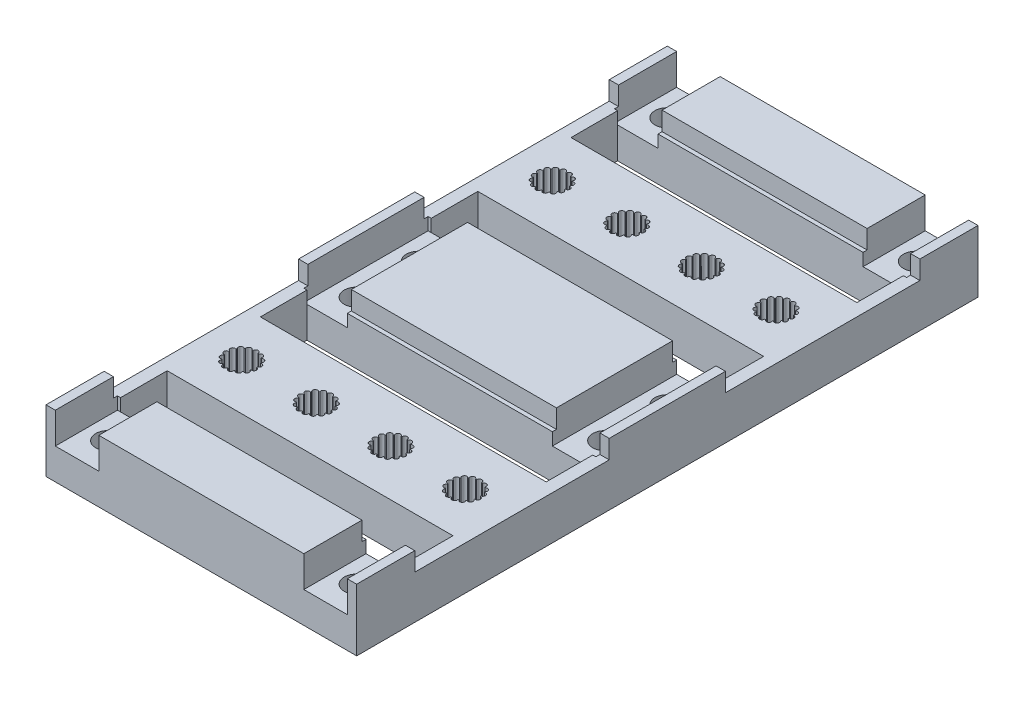
SolidWorks part; units mm, degrees
ref_plane "Front Plane" through (0, 0, 0) normal (0, 0, 1) x (1, 0, 0)
ref_plane "Top Plane" through (0, 0, 0) normal (0, 1, 0) x (1, 0, 0)
ref_plane "Right Plane" through (0, 0, 0) normal (1, 0, 0) x (0, 0, -1)
sketch "Sketch1" plane through (0, 0, 0) normal (0, 1, 0) x (1, 0, 0)
  line L0 (25, 25) -> (25, -25)
  line L1 (-20, 20) -> (20, 20)
  line L2 (-20, 20) -> (-20, -20)
  line L3 (-20, -20) -> (20, -20)
  line L4 (20, 20) -> (20, -20)
  line L5 (-20, 20) -> (20, -20) construction
  line L6 (-20, -20) -> (20, 20) construction
  line L7 (30, -16) -> (-30, -16)
  line L8 (30, -16) -> (30, 16)
  line L9 (30, 16) -> (-30, 16)
  line L10 (-30, -16) -> (-30, 16)
  line L11 (30, -16) -> (-30, 16) construction
  line L12 (30, 16) -> (-30, -16) construction
  line L13 (-25, -25) -> (25, -25)
  line L14 (-25, 25) -> (-25, -25)
  line L15 (-25, 25) -> (25, 25)
  point P0 (0, 0)
  point P6 (0, 0)
  dimension "D1" = 40
  dimension "D2" = 40
  dimension "D3" = 32
  dimension "D4" = 60
  dimension "D5" = 5
extrude "Boss-Extrude2" add sketch "Sketch1" along normal blind 10 contours L15 L0 L13 L14
sketch "Sketch2" plane through (0, 10, 0) normal (0, 1, 0) x (1, 0, 0)
  line L0 (30, -16) -> (-30, -16) construction
  line L1 (30, -16) -> (30, 16) construction
  line L2 (30, 16) -> (-30, 16) construction
  line L3 (-30, -16) -> (-30, 16) construction
  line L4 (30, -16) -> (-30, -16)
  line L5 (30, -16) -> (30, 16)
  line L6 (30, 16) -> (-30, 16)
  line L7 (-30, -16) -> (-30, 16)
  line L8 (29.65, 15.65) -> (-29.65, 15.65)
  line L9 (-29.65, -15.65) -> (-29.65, 15.65)
  line L10 (29.65, -15.65) -> (-29.65, -15.65)
  line L11 (29.65, -15.65) -> (29.65, 15.65)
  line M5 (-25, 25) -> (-25, -25)
  line M7 (25, -25) -> (25, 25)
  dimension "D1" = 0.35
extrude "Cut-Extrude1" cut sketch "Sketch2" against normal blind 3 contours L10 L8 M7 M5 | L10 L8 L9 M5 | L10 L11 L8 M7 region at (27.325, 10, 0) region at (0, 10, 0) region at (-27.325, 10, 0)
sketch "Sketch3" plane through (0, 10, 0) normal (0, 1, 0) x (1, 0, 0)
  circle A0 centre (-20, 20) radius 2
  circle A1 centre (20, 20) radius 2
  circle A2 centre (20, -20) radius 2
  circle A3 centre (-20, -20) radius 2
  dimension "D1" = 4
  dimension "D2" = 4
  dimension "D3" = 4
  dimension "D4" = 4
extrude "Cut-Extrude2" cut sketch "Sketch3" against normal blind 34
sketch "Sketch4" plane through (0, 10, 0) normal (0, 1, 0) x (1, 0, 0)
  line L0 (-25, 25) -> (25, 25) construction
  line L1 (-23.5, 15) -> (-16.5, 15)
  line L2 (-23.5, 15) -> (-23.5, 25)
  line L3 (-23.5, 25) -> (-16.5, 25)
  line L4 (-16.5, 15) -> (-16.5, 25)
  line L5 (-23.5, 15) -> (-16.5, 25) construction
  line L6 (-23.5, 25) -> (-16.5, 15) construction
  point P0 (-20, 20)
  dimension "D1" = 7
extrude "Cut-Extrude4" cut sketch "Sketch4" against normal blind 5 contours L4 L3 L2 L1
ref_plane "Plane1" through (0, 0, 0) normal (0, 0, 1) x (1, 0, 0)
ref_plane "Plane2" through (0, 0, 0) normal (-1, 0, 0) x (0, 0, 1)
mirror "Mirror1" about plane through (0, 0, 0) normal (-1, 0, 0) of "Cut-Extrude4" second plane through (0, 0, 0) second plane normal (0, 0, 1)
sketch "Sketch6" plane through (0, 7, 0) normal (0, 1, 0) x (1, 0, 0)
  line L0 (20, 20) -> (20, -20) construction
  line L1 (-20, -12) -> (20, -12)
  line L2 (-20, -12) -> (-20, 12)
  line L3 (-20, 12) -> (20, 12)
  line L4 (20, -12) -> (20, 12)
  line L5 (-20, -12) -> (20, 12) construction
  line L6 (-20, 12) -> (20, -12) construction
  line L7 (-20, 20) -> (20, 20) construction
  line L8 (-23, 15) -> (23, 15)
  line L9 (23, -15) -> (23, 15)
  line L10 (-23, -15) -> (23, -15)
  line L11 (-23, -15) -> (-23, 15)
  point P0 (0, 0)
  dimension "D1" = 8
  dimension "D2" = 3
extrude "Cut-Extrude5" cut sketch "Sketch6" against normal through all contours L1 L4 L3 L2 | L11 L10 L9 L8 L4 L1 L2 L3 region at (0, 7, 0) region at (0, 7, -14.4508)
sketch "Sketch7" plane through (0, 10, 0) normal (0, 1, 0) x (1, 0, 0)
  line L0 (23, -15) -> (23, 15) construction
  line L1 (-23, -7.5) -> (23, -7.5)
  line L2 (-23, -7.5) -> (-23, 7.5)
  line L3 (-23, 7.5) -> (23, 7.5)
  line L4 (23, -7.5) -> (23, 7.5)
  line L5 (-23, -7.5) -> (23, 7.5) construction
  line L6 (-23, 7.5) -> (23, -7.5) construction
  line L7 (-5.5, 0) -> (5.5, 0) construction
  circle A0 centre (-18.5067, 0) radius 2.25
  circle A1 centre (-18.5067, 2.25) radius 0.4
  circle A2 centre (-17.5915, 2.0555) radius 0.4
  circle A3 centre (-16.8346, 1.5055) radius 0.4
  circle A4 centre (-16.3668, 0.6953) radius 0.4
  circle A5 centre (-16.269, -0.2352) radius 0.4
  circle A6 centre (-16.5581, -1.125) radius 0.4
  circle A7 centre (-17.1842, -1.8203) radius 0.4
  circle A8 centre (-18.0389, -2.2008) radius 0.4
  circle A9 centre (-18.9745, -2.2008) radius 0.4
  circle A10 centre (-19.8292, -1.8203) radius 0.4
  circle A11 centre (-20.4552, -1.125) radius 0.4
  circle A12 centre (-20.7444, -0.2352) radius 0.4
  circle A13 centre (-20.6466, 0.6953) radius 0.4
  circle A14 centre (-20.1788, 1.5055) radius 0.4
  circle A15 centre (-19.4218, 2.0555) radius 0.4
  circle A16 centre (-4.3668, 0.6953) radius 0.4
  circle A17 centre (-4.269, -0.2352) radius 0.4
  circle A18 centre (-6.5067, 0) radius 2.25
  circle A19 centre (-4.5581, -1.125) radius 0.4
  circle A20 centre (-5.1842, -1.8203) radius 0.4
  circle A21 centre (-6.0389, -2.2008) radius 0.4
  circle A22 centre (-6.9745, -2.2008) radius 0.4
  circle A23 centre (-7.8292, -1.8203) radius 0.4
  circle A24 centre (-8.4552, -1.125) radius 0.4
  circle A25 centre (-8.7444, -0.2352) radius 0.4
  circle A26 centre (-8.6466, 0.6953) radius 0.4
  circle A27 centre (-8.1788, 1.5055) radius 0.4
  circle A28 centre (-7.4218, 2.0555) radius 0.4
  circle A29 centre (-6.5067, 2.25) radius 0.4
  circle A30 centre (-5.5915, 2.0555) radius 0.4
  circle A31 centre (-4.8346, 1.5055) radius 0.4
  circle A32 centre (7.6332, 0.6953) radius 0.4
  circle A33 centre (7.731, -0.2352) radius 0.4
  circle A34 centre (5.4933, 0) radius 2.25
  circle A35 centre (7.4419, -1.125) radius 0.4
  circle A36 centre (6.8158, -1.8203) radius 0.4
  circle A37 centre (5.9611, -2.2008) radius 0.4
  circle A38 centre (5.0255, -2.2008) radius 0.4
  circle A39 centre (4.1708, -1.8203) radius 0.4
  circle A40 centre (3.5448, -1.125) radius 0.4
  circle A41 centre (3.2556, -0.2352) radius 0.4
  circle A42 centre (3.3534, 0.6953) radius 0.4
  circle A43 centre (3.8212, 1.5055) radius 0.4
  circle A44 centre (4.5782, 2.0555) radius 0.4
  circle A45 centre (5.4933, 2.25) radius 0.4
  circle A46 centre (6.4085, 2.0555) radius 0.4
  circle A47 centre (7.1654, 1.5055) radius 0.4
  circle A48 centre (19.6332, 0.6953) radius 0.4
  circle A49 centre (19.731, -0.2352) radius 0.4
  circle A50 centre (17.4933, 0) radius 2.25
  circle A51 centre (19.4419, -1.125) radius 0.4
  circle A52 centre (18.8158, -1.8203) radius 0.4
  circle A53 centre (17.9611, -2.2008) radius 0.4
  circle A54 centre (17.0255, -2.2008) radius 0.4
  circle A55 centre (16.1708, -1.8203) radius 0.4
  circle A56 centre (15.5448, -1.125) radius 0.4
  circle A57 centre (15.2556, -0.2352) radius 0.4
  circle A58 centre (15.3534, 0.6953) radius 0.4
  circle A59 centre (15.8212, 1.5055) radius 0.4
  circle A60 centre (16.5782, 2.0555) radius 0.4
  circle A61 centre (17.4933, 2.25) radius 0.4
  circle A62 centre (18.4085, 2.0555) radius 0.4
  circle A63 centre (19.1654, 1.5055) radius 0.4
  circle A64 centre (31.6332, 0.6953) radius 0.4
  circle A65 centre (31.731, -0.2352) radius 0.4
  circle A66 centre (29.4933, 0) radius 2.25
  circle A67 centre (31.4419, -1.125) radius 0.4
  circle A68 centre (30.8158, -1.8203) radius 0.4
  circle A69 centre (29.9611, -2.2008) radius 0.4
  circle A70 centre (29.0255, -2.2008) radius 0.4
  circle A71 centre (28.1708, -1.8203) radius 0.4
  circle A72 centre (27.5448, -1.125) radius 0.4
  circle A73 centre (27.2556, -0.2352) radius 0.4
  circle A74 centre (27.3534, 0.6953) radius 0.4
  circle A75 centre (27.8212, 1.5055) radius 0.4
  circle A76 centre (28.5782, 2.0555) radius 0.4
  circle A77 centre (29.4933, 2.25) radius 0.4
  circle A78 centre (30.4085, 2.0555) radius 0.4
  circle A79 centre (31.1654, 1.5055) radius 0.4
  point P0 (0, 0)
  point P44 (-18.5067, 0)
  dimension "D2" = 4.5
  dimension "D3" = 0.8
  dimension "D1" = 15
  dimension "D5" = 5
  dimension "D4" = 15
extrude "Boss-Extrude3" add sketch "Sketch7" against normal up to surface (10 mm away) from surface contours L1 L4 L3 L2 A63 A50 A48 A49 A51 A52 A53 A54 A55 A56 A57 A58 A59 A60 A61 A62 A47 A34 A32 A33 A35 A36 A37 A38 A39 region at (0.0658, 10, 0) up to face at (0, 0, 0) starting at face at (0, 7, -15.325)
mirror "Mirror2" about plane through (-25, 10, -25) normal (0, 0, -1) of bodies 110
